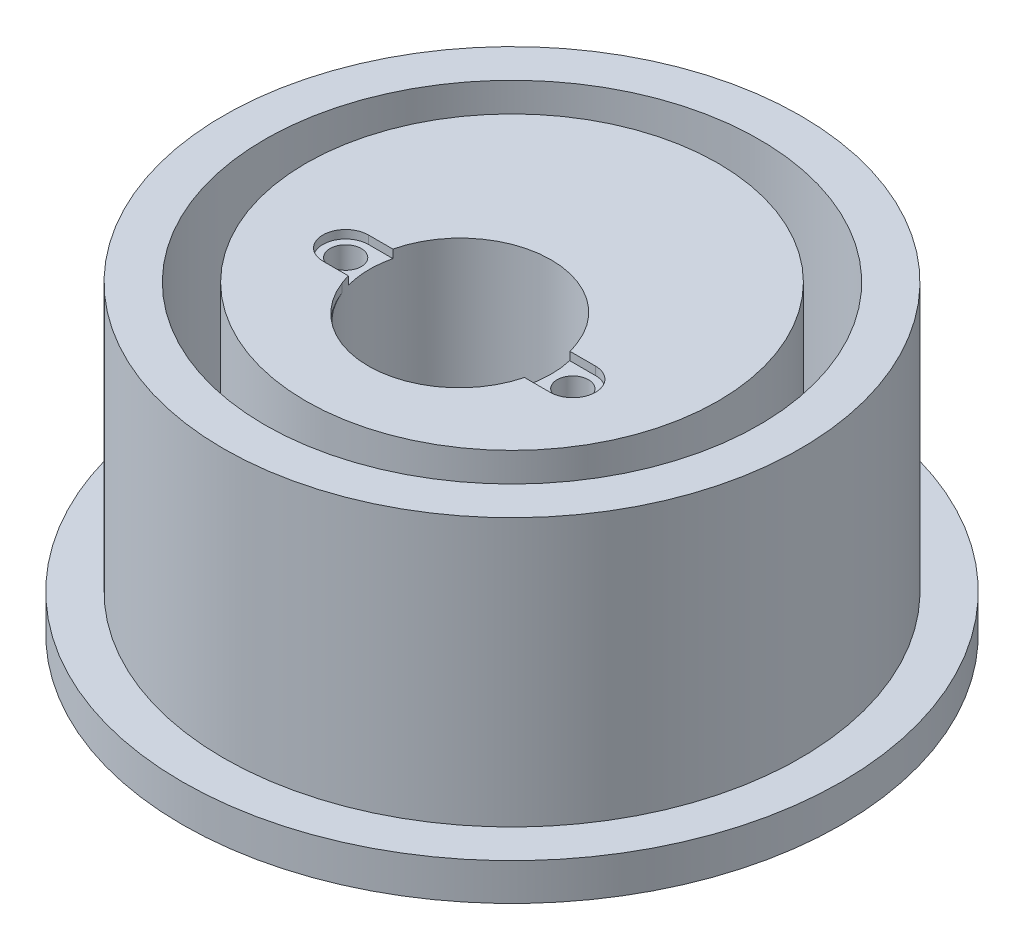
SolidWorks part; units mm, degrees
ref_plane "Front Plane" through (0, 0, 0) normal (0, 0, 1) x (1, 0, 0)
ref_plane "Top Plane" through (0, 0, 0) normal (0, 1, 0) x (1, 0, 0)
ref_plane "Right Plane" through (0, 0, 0) normal (1, 0, 0) x (0, 0, -1)
sketch "Sketch2" plane through (0, 0, 0) normal (0, 1, 0) x (1, 0, 0)
  circle A1 centre (0, 0) radius 4.4958 construction
  circle A2 centre (0, -8.001) radius 13.97 construction
  circle A4 centre (0, 0) radius 44.45
  circle A5 centre (0, 0) radius 38.1
  dimension "D1" = 8.001
  dimension "D2" = 27.94
  dimension "D3" = 8.9916
  dimension "D4" = 88.9
  dimension "D5" = 76.2
extrude "Boss-Extrude1" add sketch "Sketch2" along normal blind 6.35 contours A5 | A4 A5 region at (-43.1928, 0, 0) region at (0, 0, 0)
extrude "Boss-Extrude2" add sketch "Sketch2<3>" along normal blind 46.99
sketch "Sketch2<3>" plane through (0, 0, 0) normal (0, 1, 0) x (1, 0, 0) same geometry as "Sketch2"
sketch "Sketch3" plane through (0, 6.35, 0) normal (0, 1, 0) x (1, 0, 0)
  line L0 (0, -8.0001) -> (0, -0.0001)
  line L1 (0, -0.0001) -> (-4.5, -0.0001) construction
  line L2 (-13.5274, -4.5001) -> (-17.4719, -4.5001)
  line L3 (-17.4719, -11.5001) -> (-13.5274, -11.5001)
  line L4 (13.5835, -11.5001) -> (17.5281, -11.5001)
  line L5 (17.5281, -4.5001) -> (13.5835, -4.5001)
  circle A0 centre (0, 0) radius 31.75
  arc A1 (13.5835, -4.5001) -> (-13.5274, -4.5001) centre (0.0281, -8.0001) ccw
  arc A2 (-17.4719, -4.5001) -> (-17.4719, -11.5001) centre (-17.4719, -8.0001) ccw
  arc A3 (-13.5274, -11.5001) -> (13.5835, -11.5001) centre (0.0281, -8.0001) ccw
  arc A4 (17.5281, -11.5001) -> (17.5281, -4.5001) centre (17.5281, -8.0001) ccw
  arc A5 (-13.5274, -4.5001) -> (-13.5274, -11.5001) centre (0.0281, -8.0001) ccw
  arc A6 (13.5835, -4.5001) -> (13.5835, -11.5001) centre (0.0281, -8.0001) cw
  dimension "D1" = 63.5
extrude "Boss-Extrude4" add sketch "Sketch3" along normal blind 40.64 contours L5 A6 L4 A4 | A5 L2 A2 L3 | A0 A4 L4 A3 L3 A2 L2 A1 L5 region at (-17.0691, 6.35, 8.0001) region at (17.1253, 6.35, 8.0001) region at (-30.852, 6.35, 0)
sketch "Sketch4" plane through (0, 46.99, 0) normal (0, 1, 0) x (1, 0, 0)
  line L0 (0.1313, -8.2627) -> (0.1313, -0.2627)
  line L1 (0.1313, -0.2627) -> (-4.3687, -0.2627) construction
  line L2 (-13.4241, -4.7627) -> (-17.3687, -4.7627)
  line L3 (-17.3687, -11.7627) -> (-13.4241, -11.7627)
  line L4 (13.6868, -11.7627) -> (17.6313, -11.7627)
  line L5 (17.6313, -4.7627) -> (13.6868, -4.7627)
  circle A0 centre (0.1313, -0.2626) radius 31.75 construction
  arc A1 (13.6868, -4.7627) -> (-13.4241, -4.7627) centre (0.1313, -8.2627) ccw
  arc A2 (-17.3687, -4.7627) -> (-17.3687, -11.7627) centre (-17.3687, -8.2627) ccw
  arc A3 (-13.4241, -11.7627) -> (13.6868, -11.7627) centre (0.1313, -8.2627) ccw
  arc A4 (17.6313, -11.7627) -> (17.6313, -4.7627) centre (17.6313, -8.2627) ccw
  circle A5 centre (-17.3687, -8.2627) radius 2.413
  circle A6 centre (17.6313, -8.2627) radius 2.413
  circle M8 centre (0.0281, -8.0001) radius 14
  dimension "D1" = 63.5
  dimension "D2" = 4.826
  dimension "D3" = 35
extrude "Cut-Extrude1" cut sketch "Sketch4" against normal blind 1.27 contours L2 A2 L3 A5 M8 | A5 | A6 | L4 A4 L5 A1 A3 A6 M8 region at (-14.0712, 46.99, 8.2733) region at (13.9978, 46.99, 10.5842) region at (-17.3687, 46.99, 8.2627) region at (17.6313, 46.99, 8.2627)
extrude "Cut-Extrude2" cut sketch "Sketch4<3>" against normal blind 8.89 contours A5 | A6 region at (-17.3687, 46.99, 8.2627) region at (17.6313, 46.99, 8.2627)
sketch "Sketch4<3>" plane through (0, 46.99, 0) normal (0, 1, 0) x (1, 0, 0) same geometry as "Sketch4"
sketch "Sketch5" plane through (0, 0, 0) normal (0, -1, 0) x (1, 0, 0)
  circle A0 centre (0, 0) radius 50.8
  dimension "D1" = 101.6
extrude "Boss-Extrude5" add sketch "Sketch5" against normal blind 5.715
